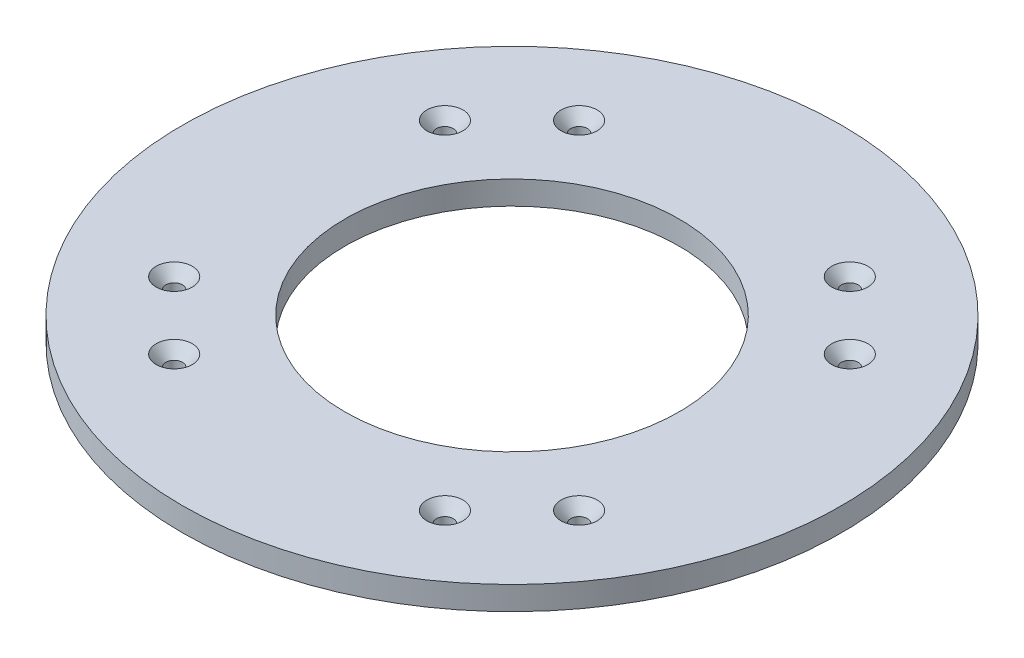
SolidWorks part; units mm, degrees
material "6061-T6 (SS)"
ref_plane "Front Plane" through (0, 0, 0) normal (0, 0, 1) x (1, 0, 0)
ref_plane "Top Plane" through (0, 0, 0) normal (0, 1, 0) x (1, 0, 0)
ref_plane "Right Plane" through (0, 0, 0) normal (1, 0, 0) x (0, 0, -1)
sketch "Sketch1" plane through (0, 0, 0) normal (0, 1, 0) x (1, 0, 0)
  line L5 (-85.725, -85.725) -> (85.725, 85.725) construction
  line L6 (-85.725, 85.725) -> (85.725, -85.725) construction
  circle A0 centre (0, 0) radius 54.61 construction
  circle A1 centre (0, 0) radius 88.9
  point P0 (0, 0)
  point P16 (-67.31, 0)
  point P18 (0, 76.2)
  dimension "D4" = 109.22
  dimension "D7" = 177.8
  dimension "D1" = 171.45
  dimension "D2" = 171.45
extrude "Boss-Extrude1" add sketch "Sketch1" along normal blind 6.35
hole_wizard "CSK for #8 Flat Head Machine Screw1" positions "Sketch3" profile "Sketch2" countersink size "#8" standard "ANSI Inch" end condition through all
sketch "Sketch3" plane through (0, 6.35, 0) normal (0, 1, 0) x (-1, 0, 0)
  line L0 (-36.5125, -54.61) -> (0, 0) construction
  line L1 (0, 0) -> (36.5125, -54.61) construction
  line L2 (36.5125, -54.61) -> (-36.5125, -54.61) construction
  line L5 (-54.61, -36.5125) -> (-54.61, 36.5125) construction
  line L8 (0, 0) -> (-54.61, -36.5125) construction
  line L11 (0, 0) -> (-54.61, 36.5125) construction
  line L14 (0, 0) -> (-36.5125, 54.61) construction
  line L15 (-36.5125, 54.61) -> (36.5125, 54.61) construction
  line L16 (36.5125, 54.61) -> (0, 0) construction
  line L17 (0, 0) -> (54.61, 36.5125) construction
  line L18 (54.61, 36.5125) -> (54.61, -36.5125) construction
  line L19 (54.61, -36.5125) -> (0, 0) construction
  point P0 (36.5125, -54.61)
  point P1 (-36.5125, -54.61)
  point P19 (36.5125, 54.61)
  point P21 (-36.5125, 54.61)
  point P23 (-54.61, -36.5125)
  point P25 (-54.61, 36.5125)
  point P27 (54.61, 36.5125)
  point P29 (54.61, -36.5125)
  dimension "D1" = 73.025
  dimension "D3" = 109.22
sketch "Sketch2" plane through (-36.5125, 6.35, -54.61) normal (1, 0, 0) x (0, 0, 1)
  line L0 (0, 0) -> (0, 6.35)
  line L1 (0, 6.35) -> (2.2479, 6.35)
  line L2 (2.2479, 6.35) -> (2.2479, 3.0265)
  line L3 (2.2479, 3.0265) -> (4.8788, 0)
  line L5 (4.8788, 0) -> (0, 0)
  line L6 (-2.2479, 3.0265) -> (-4.8788, 0) construction
  line L11 (0, -6.35) -> (0, 107.95) construction
  dimension "Thru Hole Dia." = 4.4958
  dimension "Thru Hole Depth" = 6.35
  dimension "Near C'Sink Dia." = 9.7576
  dimension "Near C'Sink Angle" = 82
ref_axis "Axis1" through (0, 0, 0) along (0, 1, 0)
pattern_circular "CirPattern1" count 2 over 360 about axis through (0, 0, 0) along (0, 1, 0) of "CSK for #8 Flat Head Machine Screw1"
sketch "Sketch4" plane through (0, 6.35, 0) normal (0, 1, 0) x (1, 0, 0)
  circle A0 centre (0, 0) radius 45.085
  dimension "D1" = 90.17
extrude "Cut-Extrude1" cut sketch "Sketch4" against normal through all
